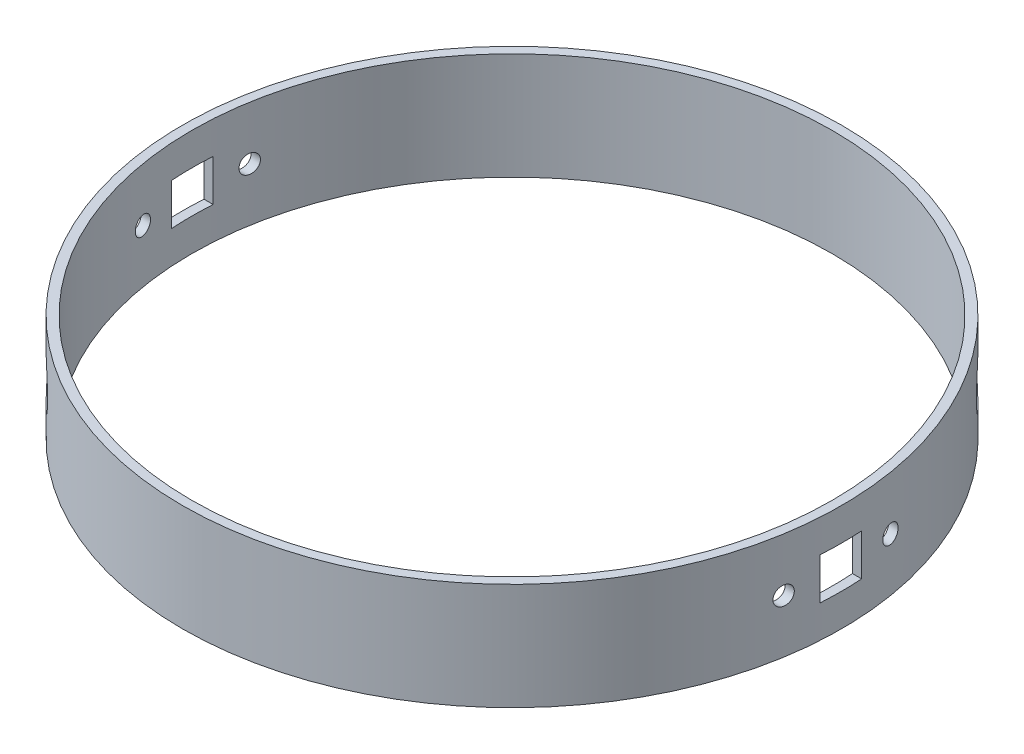
SolidWorks part; units mm, degrees
material "A-Glass Fiber"
ref_plane "Front Plane" through (0, 0, 0) normal (0, 0, 1) x (1, 0, 0)
ref_plane "Top Plane" through (0, 0, 0) normal (0, 1, 0) x (1, 0, 0)
ref_plane "Right Plane" through (0, 0, 0) normal (1, 0, 0) x (0, 0, -1)
sketch "Sketch1" plane through (0, 0, 0) normal (0, 1, 0) x (1, 0, 0)
  circle A0 centre (0, 0) radius 78.359
  circle A1 centre (0, 0) radius 76.1746
  dimension "D1" = 156.718
  dimension "D2" = 152.3492
extrude "Boss-Extrude1" add sketch "Sketch1" along normal blind 25.4
sketch "Sketch2" plane through (0, 0, 0) normal (1, 0, 0) x (0, 0, -1)
  line L0 (-78.359, 0) -> (78.359, 0) construction
  line L7 (0, 12.7) -> (0, 14.52) construction
  line L12 (4.953, 7.747) -> (-4.953, 7.747)
  line L13 (0, 25.4) -> (0, 0) construction
  line L14 (76.1746, 25.4) -> (-76.1746, 25.4) construction
  line L15 (-78.359, 0) -> (78.359, 0)
  line L16 (76.1746, 25.4) -> (-76.1746, 25.4)
  line L17 (-28.7231, 12.7) -> (26.1298, 12.7) construction
  line L25 (4.953, 7.747) -> (4.953, 17.653)
  line L26 (4.953, 17.653) -> (-4.953, 17.653)
  line L27 (-4.953, 7.747) -> (-4.953, 17.653)
  line L28 (4.953, 7.747) -> (-4.953, 17.653) construction
  line L29 (4.953, 17.653) -> (-4.953, 7.747) construction
  circle A0 centre (-12.7, 12.7) radius 2.1831
  circle A1 centre (12.7, 12.7) radius 2.1831
  point P0 (0, 9.85)
  point P14 (0, 3.175)
  point P27 (0, 12.7)
  dimension "D4" = 9.906
  dimension "D8" = 4.3663
  dimension "D1" = 12.7
  dimension "D5" = 9.906
extrude "Cut-Extrude1" cut sketch "Sketch2" along normal through all both and the other way through all contours L25 L12 L27 L26 | A1 | A0
ref_plane "Plane1" through (0, 0, 0) normal (0.9973, 0, 0.0728) x (0, -1, 0)
ref_plane "Plane2" through (0, 12.7, 0) normal (0, 1, 0) x (1, 0, 0)
mirror "Mirror2" about plane through (0, 0, 0) normal (1, 0, 0) of "Cut-Extrude1", "Boss-Extrude1" second plane through (0, 12.7, 0) second plane normal (0, 1, 0)
ref_plane "Plane3" through (0, 0, 0) normal (0.7071, 0, -0.7071) x (-0.7071, 0, -0.7071)
sketch "Sketch3" plane through (0, 0, 0) normal (0.7071, 0, -0.7071) x (-0.7071, 0, -0.7071)
  line L0 (0, 25.4) -> (0, 0) construction
  line L1 (-78.359, 0) -> (78.359, 0) construction
  circle A0 centre (0, 12.7) radius 6.35
  point P4 (0, 8.1096)
  dimension "D1" = 12.7
  dimension "D2" = 12.7
extrude "Cut-Extrude2" cut sketch "Sketch3" against normal through all both and the other way through all
equation "\"Bodytube_OD\" = 6.17in"
equation "\"Bodytube_ID\" = 5.998in"
equation "\"D1@Sketch1\"=\"Bodytube_OD\""
equation "\"D2@Sketch1\"= \"Bodytube_ID\""
equation "\"Camera_Cutout_Width\"=10mm"
equation "\"Camera_Cutout_Height\"=7mm"
equation "\"Fwd_Tube_Length\" = 40in"
equation "\"BKHD_Screw_Diam\"= 3.5mm"
equation "\"Fwd_BKHD_From_Top\" = 18in"
equation "\"Shear_Screw_Diameter\" = 0.086in"
equation "\"Shear_Screw_Coupler_Location\" = 4.5in"
equation "\"Motor_OD\" = 4in"
equation "\"Mid_Coupler_Length\" = 13in"
equation "\"Aft_Section_Length\"= 39in"
equation "\"AB_Coupler_OD_Length\"= 1in"
equation "\"AB_Coupling_Section_Length\"= 0.375in"
equation "\"AB_Coupler_Length\"= \"AB_Coupler_OD_Length\" + \"AB_Coupling_Section_Length\" * 2"
equation "\"Cutout_Angle\" = 80"
equation "\"AB_Paddle_Height\" = 0.375in"
equation "\"AB_Coupler_Num_Screws\"= 4"
equation "\"AB_BKHD_Thickness\" = 0.375in"
equation "\"AB_Mount_From_Bottom\" = 23.175in"
equation "\"Num_Cutouts\" = 3"
equation "\"AB_Coupler_OD\"= 6.17in"
equation "\"AB_Coupler_ID\"= 5.75in"
equation "\"AB_Coupler_Surface_Diameter\"= 5.998in"
equation "\"AB_Coupling_Screw_Diameter\"= 0.15748in"
equation "\"AB_Central_Bushing_Length\" = .4724in"
equation "\"Lead_Screw_Dist\" = 3.4in"
equation "\"Lead_Screw_Diam\" = 0.386in"
equation "\"Lead_Screw_Length\" = (\"Mid_Coupler_Length\" + 2*0.375in + 2*0.5in)"
equation "\"Paddle_Pin_Offset\" = .25in"
equation "\"Paddle_Pin_Radius\" = 2.25in"
equation "\"SS_Paddle_Pin_Radius\" = 2.25*0.66in"
equation "\"Paddle_Gear_OD\" = 3.2in"
equation "\"Drive_Gear_OD\" = 1.7in"
equation "\"Fin_Thickness\"= .118in"
equation "\"Guiderail_Cutout_Diameter\"= 1.5in"
equation "\"DB9_Hole_Dist\" = 25mm"
equation "\"DB9_Relief_Width\" = 0.47in"
equation "\"DB9_Relief_Hole_Offset\" = 0.09in"
equation "\"Airbrakes_Wire_Hole_Dia\" = .25in"
equation "\"Airbrakes_Wire_Hole_Dist\" = 1.1in"
equation "\"Servo_Gear_Offset\" = 0.5in"
equation "\"FWD_Shear_Screw_Dist\" = 1.5in"
equation "\"Camera_Screw_Dia\" = 0.216535"
equation "\"Camera_Hole_Angle\" = atn ( 2 / 3 * tan ( 12.5deg ) )"
equation "\"Coupler_OD\" = 5.998"
equation "\"Coupler_ID\" = 5.8"
equation "\"Mounting_Bracket_Centerhole_DIA\" = 0.4in"
equation "\"Drive_Gear_Shaft_DIA\" = \"Mounting_Bracket_Centerhole_DIA\" - 0.02in"
equation "\"Drive_Gear_Fillet\" = 0.22in"
equation "\"Drive_Gear_ID\" = 0.62in"
equation "\"Drive_Gear_Offset\" = 0.01in"
